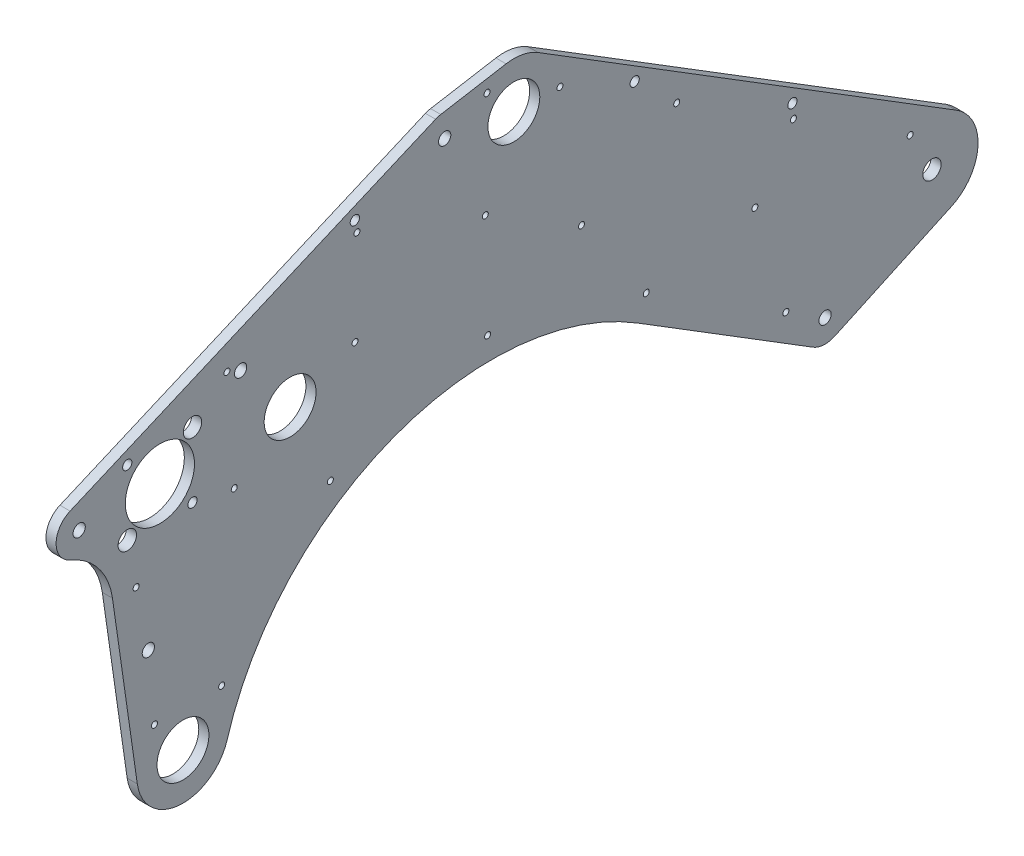
SolidWorks part; units mm, degrees
material "Acrylic (Medium-high impact)"
ref_plane "Front" through (0, 0, 0) normal (0, 0, 1) x (1, 0, 0)
ref_plane "Top" through (0, 0, 0) normal (0, 1, 0) x (1, 0, 0)
ref_plane "Right" through (0, 0, 0) normal (1, 0, 0) x (0, 0, -1)
sketch "Sketch1" plane through (0, 0, 0) normal (1, 0, 0) x (0, 0, -1)
  line L0 (-109.5375, -69.85) -> (-109.5375, -196.85)
  line L1 (-109.5375, -196.85) -> (-160.3375, -196.85)
  line L2 (-192.0875, -165.1) -> (-192.0875, -101.6)
  line L3 (-160.3375, -69.85) -> (-109.5375, -69.85)
  line L4 (-28.6872, -260.35) -> (-968.3377, -260.35) construction
  line L5 (-414.3375, -165.1) -> (-414.3375, -101.6) construction
  line L6 (-101.6, -57.15) -> (-76.2, -57.15)
  line L7 (-101.6, -57.15) -> (-101.6, -82.55)
  line L8 (-101.6, -82.55) -> (-76.2, -82.55)
  line L9 (-76.2, -57.15) -> (-76.2, -82.55)
  line L10 (-160.3375, 152.4) -> (-109.5375, 152.4) construction
  line L11 (-412.4442, -70.6452) -> (-160.3375, -101.6) construction
  line L12 (-353.4405, 63.4068) -> (-160.3375, -101.6) construction
  line L13 (-230.2306, 142.5945) -> (-160.3375, -101.6) construction
  line L14 (-435.3258, -60.5737) -> (-376.322, 73.4782)
  line L15 (-330.5589, 53.3353) -> (-389.5627, -80.7166)
  line L16 (-366.9572, 84.4377) -> (-243.7472, 163.6254)
  line L17 (-109.5375, -69.85) -> (-109.5375, 357.098) construction
  line L18 (-216.7139, 121.5636) -> (-339.9238, 42.3759)
  line L19 (-515.9375, 289.2974) -> (-515.9375, -104.2984) construction
  line L22 (-400.2568, 65.0845) -> (-387.5568, -68.2751)
  line L23 (-437.3316, -73.0152) -> (-450.0316, 60.3444)
  circle A0 centre (0, 0) radius 5.0419
  circle A1 centre (-412.4442, -70.6452) radius 11.557
  circle A2 centre (-353.4405, 63.4068) radius 11.557
  circle A3 centre (-230.2306, 142.5945) radius 11.557
  arc A4 (-160.3375, -196.85) -> (-192.0875, -165.1) centre (-160.3375, -165.1) cw
  arc A5 (-192.0875, -101.6) -> (-160.3375, -69.85) centre (-160.3375, -101.6) cw
  circle A6 centre (-309.0551, -144.1658) radius 120.65
  arc A7 (-414.3375, -101.6) -> (-160.3375, 152.4) centre (-160.3375, -101.6) cw construction
  circle A12 centre (-425.1442, 62.7144) radius 31.75
  arc A15 (-389.5627, -80.7166) -> (-435.3258, -60.5737) centre (-412.4442, -70.6452) cw
  arc A16 (-376.322, 73.4782) -> (-330.5589, 53.3353) centre (-353.4405, 63.4068) cw
  arc A17 (-339.9238, 42.3759) -> (-366.9572, 84.4377) centre (-353.4405, 63.4068) cw
  arc A18 (-243.7472, 163.6254) -> (-216.7139, 121.5636) centre (-230.2306, 142.5945) cw
  arc A21 (-450.0316, 60.3444) -> (-400.2568, 65.0845) centre (-425.1442, 62.7144) cw
  arc A22 (-387.5568, -68.2751) -> (-437.3316, -73.0152) centre (-412.4442, -70.6452) cw
  point P23 (-435.9059, 61.2473)
  point P24 (0, 0)
  point P33 (-422.6416, 62.9291)
  point P36 (-152.8895, 51.1296)
  point P48 (-308.6891, -153.6627)
  point P49 (-309.0551, -144.1658)
  circle B0 centre (-230.2306, 142.5945) radius 25
  circle B1 centre (-353.4405, 63.4068) radius 25
  circle B2 centre (-412.4442, -70.6452) radius 25
  circle B3 centre (-425.1442, 62.7144) radius 25
  dimension "D1" = 10.0838
  dimension "D2" = 23.114
  dimension "D4" = 31.75
  dimension "D10" = 241.3
  dimension "D19" = 63.5
  dimension "D26" = 70.6452
  dimension "D27" = 412.4442
  dimension "D3" = 127
  dimension "D5" = 82.55
  dimension "D6" = 190.5
  dimension "D7" = 25.4
  dimension "D8" = 7.9375
  dimension "D9" = 203.2
  dimension "D12" = 101.6
  dimension "D13" = 57.15
  dimension "D14" = 33.514
  dimension "D15" = 33.514
  dimension "D16" = 7
  dimension "D24" = 406.4
  dimension "D21" = 12.7
  dimension "D11" = 222.25
sketch_block_instance "Block1-1"
sketch_block "Block1" parameters "D1"=50
sketch_block_instance "Block2-1"
sketch_block "Block2" parameters "D1"=40
sketch_block_instance "Block3-1"
sketch_block "Block3" parameters "D1"=40
sketch_block_instance "Block4-1"
sketch_block "Block4" parameters "D1"=50
other "Belt1"
other "Belt2"
other "Belt4"
sketch "Sketch3" plane through (0, 0, 0) normal (1, 0, 0) x (0, 0, -1)
  line L0 (-412.4442, -70.6452) -> (0, 0) construction
  line L1 (0, 0) -> (-58.8496, -41.2069) construction
  line L2 (0, 0) -> (-70.6452, 412.4442) construction
  line L3 (0, 0) -> (-41.2069, 58.8496) construction
  line L4 (-58.8496, -41.2069) -> (-64.0291, -10.9672) construction
  line L5 (-41.2069, 58.8496) -> (-10.9672, 64.0291) construction
  line L6 (-41.2069, 58.8496) -> (-58.8496, -41.2069)
  line L7 (-4.2676, 268.3428) -> (-41.2069, 58.8496)
  line L8 (0, 0) -> (142.5945, 230.2306) construction
  line L9 (0, 0) -> (-230.2306, 142.5945) construction
  line L10 (-230.2306, 142.5945) -> (-199.9405, -34.2466) construction
  line L11 (142.5945, 230.2306) -> (-34.2466, 199.9405) construction
  circle A0 centre (-70.6452, 412.4442) radius 25.4
  dimension "D1" = 50.8
  dimension "D2" = 90
  dimension "D3" = 101.6
  dimension "D4" = 212.725
  dimension "D5" = 80
sketch "Sketch2" plane through (0, 0, 0) normal (1, 0, 0) x (0, 0, -1)
  line L0 (-437.5873, -74.249) -> (-451.2631, 21.1636)
  line L1 (-474.5957, 74.3881) -> (-273.3321, 160.6182)
  line L2 (-412.4442, -70.6452) -> (-412.4442, 0) construction
  line L4 (13.3742, 21.5938) -> (-216.8564, 164.1883)
  line L7 (-65.5367, -52.0038) -> (-161.9352, 7.7012)
  line L10 (-53.5189, -52.734) -> (10.6613, -23.0542)
  line L11 (-270.4777, 161.4617) -> (-234.5248, 167.6289)
  line L13 (-443.1047, 44.7539) -> (-407.1837, 80.675) construction
  line L14 (-443.1047, 80.675) -> (-407.1837, 44.7539) construction
  circle A0 centre (-230.2306, 142.5945) radius 14.2875
  circle A1 centre (-353.4405, 63.4068) radius 14.2875
  circle A2 centre (-412.4442, -70.6452) radius 14.2875
  circle A3 centre (-425.1442, 62.7144) radius 19.05
  circle A9 centre (0, 0) radius 5.0419 construction
  circle A10 centre (0, 0) radius 5.0419
  arc A13 (-437.5873, -74.249) -> (-388.1208, -77.9618) centre (-412.4442, -70.6452) ccw
  arc A16 (10.6613, -23.0542) -> (13.3742, 21.5938) centre (0, 0) ccw
  arc A18 (-161.9352, 7.7012) -> (-388.1208, -77.9618) centre (-242.1805, -121.8614) ccw
  circle A19 centre (-58.8496, -41.2069) radius 3.3782
  circle A22 centre (-268.3306, 148.9445) radius 3.3782
  arc A23 (-273.3321, 160.6182) -> (-270.4777, 161.4617) centre (-268.3306, 148.9445) cw
  circle A24 centre (-230.2306, 142.5945) radius 25.4 construction
  circle A27 centre (-407.1837, 80.675) radius 5.08
  circle A28 centre (-443.1047, 80.675) radius 2.5527
  circle A29 centre (-443.1047, 44.7539) radius 5.08
  circle A30 centre (-407.1837, 44.7539) radius 2.5527
  circle A31 centre (-425.1442, 62.7144) radius 25.4 construction
  circle A32 centre (-469.5942, 62.7144) radius 3.3782
  arc A34 (-474.5957, 74.3881) -> (-474.4401, 50.9753) centre (-469.5942, 62.7144) ccw
  arc A35 (-474.4401, 50.9753) -> (-451.2631, 21.1636) centre (-488.9776, 15.7578) cw
  circle A37 centre (-425.1442, 62.7144) radius 31.75 construction
  circle A38 centre (-469.5942, 62.7144) radius 7.9375 construction
  circle A39 centre (-431.4942, -13.4856) radius 3.3782
  circle A40 centre (-431.4942, -13.4856) radius 7.9375 construction
  circle A41 centre (-380.6942, 94.4644) radius 3.3782
  arc A42 (-65.5367, -52.0038) -> (-53.5189, -52.734) centre (-58.8496, -41.2069) ccw
  arc A43 (-234.5248, 167.6289) -> (-216.8564, 164.1883) centre (-230.2306, 142.5945) cw
  circle A44 centre (-353.4405, 63.4068) radius 11.557 construction
  point P5 (0, 0)
  point P11 (-422.5469, 53.7636)
  point P14 (-455.962, 46.3497)
  point P45 (-425.1442, 62.7144)
  dimension "D1" = 28.575
  dimension "D2" = 38.1
  dimension "D3" = 6.35
  dimension "D4" = 50.8
  dimension "D5" = 12.7
  dimension "D6" = 38.1
  dimension "D7" = 25.4
  dimension "D8" = 152.4
  dimension "D10" = 6.7564
  dimension "D11" = 6.7564
  dimension "D12" = 15.875
  dimension "D13" = 12.7
  dimension "D17" = 15.875
  dimension "D18" = 5.1054
  dimension "D19" = 10.16
  dimension "D20" = 50.8
  dimension "D21" = 25.4
  dimension "D22" = 38.1
  dimension "D23" = 6.35
  dimension "D16" = 44.45
  dimension "D15" = 31.75
  dimension "D24" = 76.2
  dimension "D25" = 44.45
  dimension "D9" = 12.7
extrude "Boss-Extrude1" add sketch "Sketch2" along normal blind 5.588
sketch "Sketch4" plane through (5.588, 0, 0) normal (1, 0, 0) x (0, 0, -1)
  line L0 (-353.4405, 63.4068) -> (-230.2306, 142.5945) construction
  line L1 (-273.3321, 160.6182) -> (-474.5957, 74.3881) construction
  line L3 (-317.8021, 134.657) -> (-434.5389, 84.6419) construction
  line L4 (-434.5389, 84.6419) -> (-425.1442, 62.7144) construction
  line L6 (13.3742, 21.5938) -> (-216.8564, 164.1883) construction
  line L11 (-250.5793, 177.6054) -> (-163.7093, 123.8021) construction
  line L12 (-163.7093, 123.8021) -> (-76.8393, 69.9987) construction
  line L13 (-76.8393, 69.9987) -> (10.0307, 16.1953) construction
  line L14 (-250.5793, 177.6054) -> (-268.3306, 148.9445) construction
  line L15 (0, 0) -> (10.0307, 16.1953) construction
  circle A4 centre (-317.8021, 134.657) radius 2.5527
  circle A5 centre (-163.7093, 123.8021) radius 2.5527
  circle A6 centre (-76.8393, 69.9987) radius 2.5527
  point P4 (0, 0)
  point P6 (0, 0)
  point P7 (-425.1442, 62.7144)
  dimension "D1" = 6.35
  dimension "D2" = 5.1054
  dimension "D3" = 127
  dimension "D6" = 6.35
extrude "Cut-Extrude1" cut sketch "Sketch4" against normal through all
sketch "Sketch6" plane through (5.588, 0, 0) normal (1, 0, 0) x (0, 0, -1)
  line L0 (-12.0136, 22.3793) -> (-76.2859, 62.1867) construction
  line L1 (-388.2238, 97.5771) -> (-316.6035, 128.2623) construction
  line L2 (-316.6035, 128.2623) -> (-244.9832, 158.9475) construction
  line L3 (-391.1166, -50.615) -> (-331.2473, 17.1534) construction
  line L4 (-58.8496, -41.2069) -> (-155.2481, 18.4981)
  line L5 (-58.8496, -41.2069) -> (-155.2481, 18.4981) construction
  line L6 (-331.2473, 17.1534) -> (-244.6597, 43.22) construction
  line L7 (-244.6597, 43.22) -> (-157.3284, 19.7653) construction
  line L8 (-157.3284, 19.7653) -> (-80.4433, -27.8327) construction
  line L9 (-76.2859, 62.1867) -> (-140.5583, 101.9941) construction
  line L10 (-273.3321, 160.6182) -> (-474.5957, 74.3881) construction
  line L11 (13.3742, 21.5938) -> (-216.8564, 164.1883) construction
  line L12 (-140.5583, 101.9941) -> (-204.8306, 141.8015) construction
  line L13 (-438.2413, 19.8239) -> (-428.1368, -50.6726) construction
  line L14 (-451.2631, 21.1636) -> (-437.5873, -74.249) construction
  line L15 (-245.9565, 101.0806) -> (-317.695, 76.4727) construction
  line L16 (-317.695, 76.4727) -> (-384.2067, 40.0286) construction
  line L17 (-244.9832, 158.9475) -> (-245.9565, 101.0806) construction
  line L18 (-245.9565, 101.0806) -> (-204.8306, 141.8015) construction
  line L19 (-245.9565, 101.0806) -> (-244.6597, 43.22) construction
  line L20 (-438.2413, 19.8239) -> (-384.2067, 40.0286) construction
  line L21 (-384.2067, 40.0286) -> (-388.2238, 97.5771) construction
  line L22 (-384.2067, 40.0286) -> (-331.2473, 17.1534) construction
  line L23 (-336.2733, 119.8349) -> (-299.1168, 33.1104) construction
  line L24 (-157.3284, 19.7653) -> (-192.9828, 69.8613) construction
  line L25 (-192.9828, 69.8613) -> (-140.5583, 101.9941) construction
  line L26 (-245.9565, 101.0806) -> (-192.9828, 69.8613) construction
  line L27 (-76.2859, 62.1867) -> (-97.4877, 30.5308) construction
  line L28 (-97.4877, 30.5308) -> (-80.4433, -27.8327) construction
  line L29 (-97.4877, 30.5308) -> (-157.3284, 19.7653) construction
  circle A0 centre (-12.0136, 22.3793) radius 1.651
  circle A1 centre (-157.3284, 19.7653) radius 1.651
  circle A2 centre (-76.2859, 62.1867) radius 1.651
  circle A3 centre (-244.6597, 43.22) radius 1.651
  circle A4 centre (-244.9832, 158.9475) radius 1.651
  circle A5 centre (-331.2473, 17.1534) radius 1.651
  circle A6 centre (-391.1166, -50.615) radius 1.651
  circle A7 centre (-438.2413, 19.8239) radius 1.651
  circle A8 centre (-316.6035, 128.2623) radius 1.651
  circle A9 centre (-388.2238, 97.5771) radius 1.651
  circle A10 centre (-140.5583, 101.9941) radius 1.651
  circle A11 centre (-80.4433, -27.8327) radius 1.651
  circle A12 centre (-268.3306, 148.9445) radius 3.3782 construction
  circle A13 centre (-407.1837, 80.675) radius 5.08 construction
  arc A14 (-155.2481, 18.4981) -> (-400.2825, -74.3035) centre (-242.1805, -121.8614) ccw
  arc A15 (-155.2481, 18.4981) -> (-400.2825, -74.3035) centre (-242.1805, -121.8614) ccw construction
  circle A16 centre (0, 0) radius 5.0419 construction
  circle A17 centre (-428.1368, -50.6726) radius 1.651
  circle A18 centre (-204.8306, 141.8015) radius 1.651
  circle A19 centre (-230.2306, 142.5945) radius 14.2875 construction
  circle A20 centre (-412.4442, -70.6452) radius 14.2875 construction
  circle A21 centre (-443.1047, 44.7539) radius 5.08 construction
  circle A22 centre (-245.9565, 101.0806) radius 1.651
  circle A23 centre (-384.2067, 40.0286) radius 1.651
  circle A24 centre (-317.695, 76.4727) radius 1.651
  circle A25 centre (-192.9828, 69.8613) radius 1.651
  circle A26 centre (-97.4877, 30.5308) radius 1.651
  dimension "D1" = 3.302
  dimension "D2" = 12.7
  dimension "D5" = 12.7
  dimension "D7" = 25.4
  dimension "D3" = 25.4
  dimension "D4" = 25.4
  dimension "D6" = 25.4
  dimension "D8" = 12.7
  dimension "D9" = 25.4
  dimension "D10" = 25.4
  dimension "D11" = 12.7
  dimension "D12" = 25.4
  dimension "D13" = 25.4
  dimension "D14" = 38.1
extrude "Cut-Extrude2" cut sketch "Sketch6" against normal through all
